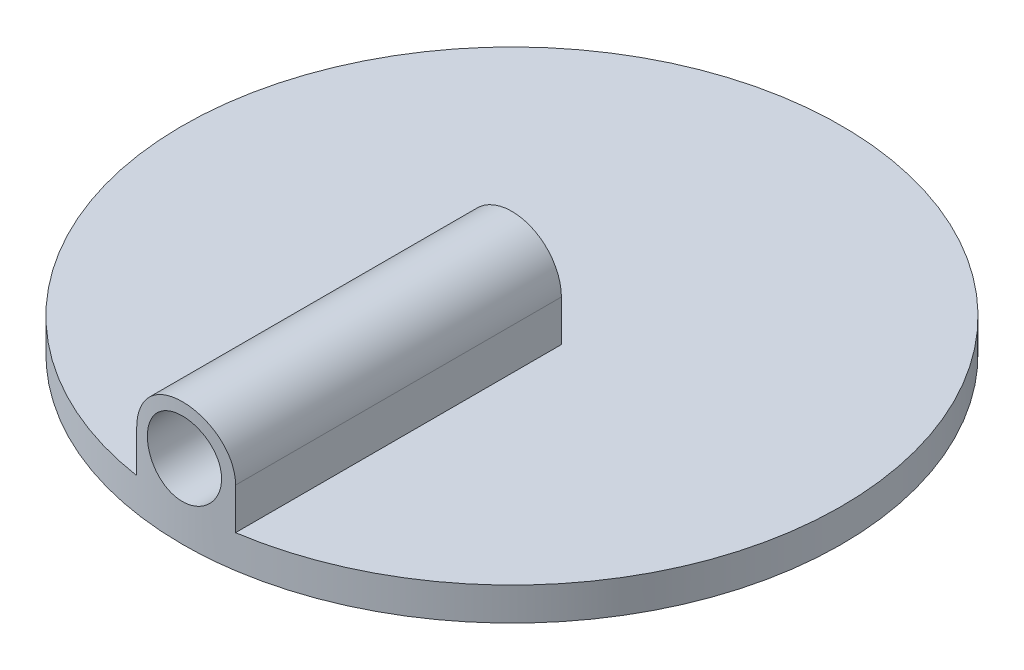
SolidWorks part; units mm, degrees
ref_plane "Front Plane" through (0, 0, 0) normal (0, 0, 1) x (1, 0, 0)
ref_plane "Top Plane" through (0, 0, 0) normal (0, 1, 0) x (1, 0, 0)
ref_plane "Right Plane" through (0, 0, 0) normal (1, 0, 0) x (0, 0, -1)
sketch "Sketch1" plane through (0, 0, 0) normal (0, 1, 0) x (1, 0, 0)
  circle A0 centre (0, 0) radius 20
  circle A1 centre (0, 0) radius 3
  dimension "D1" = 40
  dimension "D2" = 6
extrude "Boss-Extrude1" add sketch "Sketch1" along normal blind 2 contours A0
sketch "Sketch4" plane through (0, 0, 0) normal (0, 0, 1) x (1, 0, 0)
  line L0 (20, 2) -> (-20, 2) construction
  line L1 (-3, 4.5) -> (-3, 2)
  line L2 (-3, 2) -> (3, 2)
  line L3 (3, 2) -> (3, 4.5)
  circle A0 centre (0, 4.5) radius 2.25
  arc A1 (3, 4.5) -> (-3, 4.5) centre (0, 4.5) ccw
  point P6 (0, 0)
  point P10 (0, 0)
  dimension "D1" = 4.5
  dimension "D2" = 4.5
  dimension "D4" = 6
  dimension "D3" = 2.5
extrude "Boss-Extrude2" add sketch "Sketch4" along normal up to surface and the other way blind 0.0001 up to face at (0, 2, 20)
